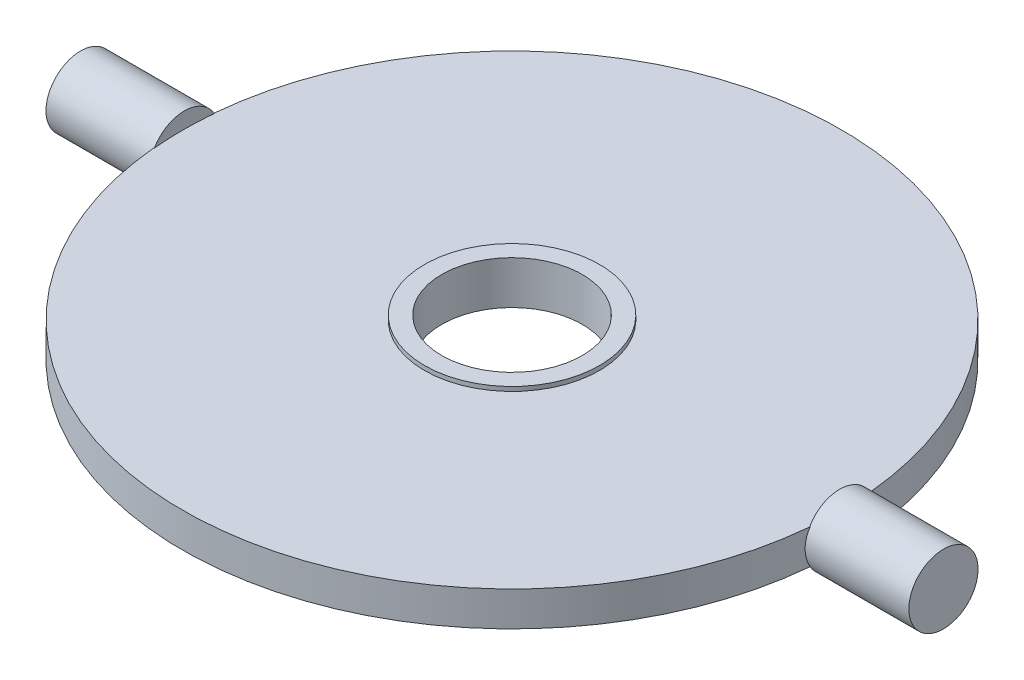
SolidWorks part; units mm, degrees
ref_plane "Front Plane" through (0, 0, 0) normal (0, 0, 1) x (1, 0, 0)
ref_plane "Top Plane" through (0, 0, 0) normal (0, 1, 0) x (1, 0, 0)
ref_plane "Right Plane" through (0, 0, 0) normal (1, 0, 0) x (0, 0, -1)
sketch "Sketch1" plane through (0, 0, 0) normal (0, 1, 0) x (1, 0, 0)
  line L0 (-76.4354, 0) -> (76.4354, 0) construction
  line L1 (-49.8894, 4) -> (-49.8894, -4)
  line L2 (0, 38.1) -> (0, -38.1) construction
  line L3 (-49.8894, 4) -> (-37.8894, 4)
  line L4 (-49.8894, -4) -> (-37.8894, -4)
  line L5 (49.8894, -4) -> (37.8894, -4)
  line L6 (49.8894, 4) -> (49.8894, -4)
  line L7 (49.8894, 4) -> (37.8894, 4)
  line L8 (-49.8894, 0) -> (-38.1, 0)
  line L9 (49.8894, 0) -> (38.1, 0)
  circle A0 centre (0, 0) radius 38.1
  circle A1 centre (0, 0) radius 8.125
  circle A2 centre (0, 0) radius 10.125
  point P6 (0, 0)
  point P9 (-49.8894, 0)
  dimension "D1" = 76.2
  dimension "D4" = 16.25
  dimension "D2" = 8
  dimension "D3" = 12
  dimension "D5" = 2
extrude "Boss-Extrude1" add sketch "Sketch1" along normal mid plane 4 contours A0 L1 region at (0, 0, -37.0224)
revolve "Revolve1" add sketch "Sketch1<6>" angle 360 about L0 region at (-43.9595, 0, 2.0059) region at (43.9595, 0, 2.0059)
sketch "Sketch1<6>" plane through (0, 0, 0) normal (0, 1, 0) x (1, 0, 0) same geometry as "Sketch1"
extrude "Boss-Extrude2" add sketch "Sketch1<7>" along normal mid plane 5 contours A2 A1 region at (-9.8386, 0, 0)
sketch "Sketch1<7>" plane through (0, 0, 0) normal (0, 1, 0) x (1, 0, 0) same geometry as "Sketch1"
